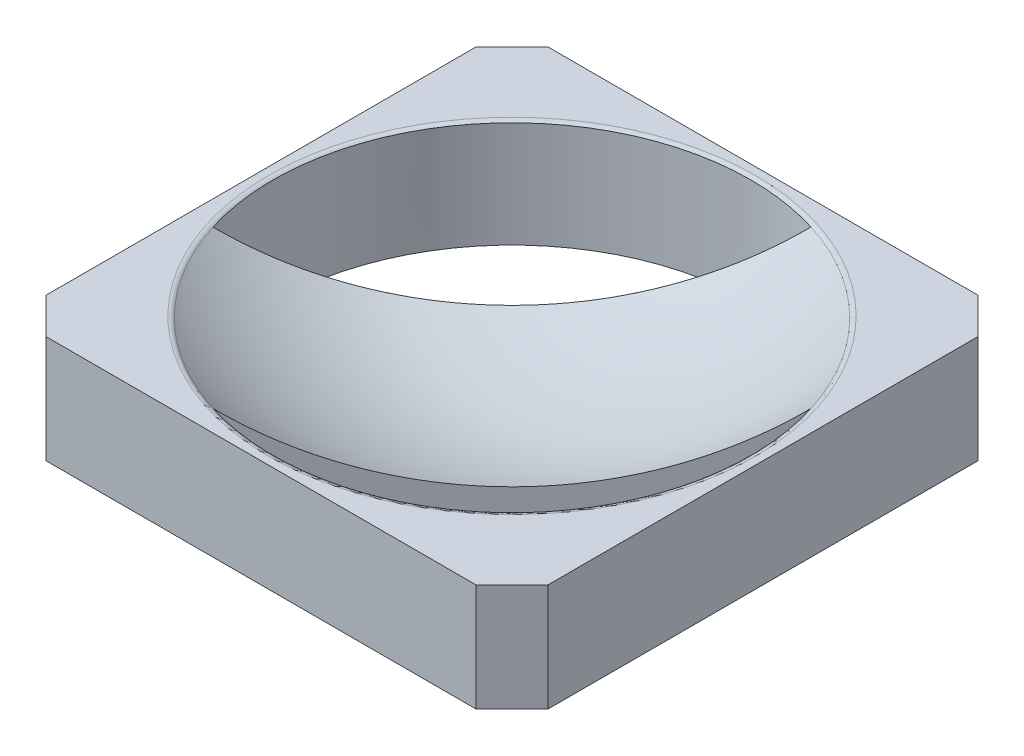
SolidWorks part; units mm, degrees
ref_plane "Front Plane" through (0, 0, 0) normal (0, 0, 1) x (1, 0, 0)
ref_plane "Top Plane" through (0, 0, 0) normal (0, 1, 0) x (1, 0, 0)
ref_plane "Right Plane" through (0, 0, 0) normal (1, 0, 0) x (0, 0, -1)
sketch "Sketch1" plane through (0, 0, 0) normal (0, 1, 0) x (1, 0, 0)
  line L1 (0, 0) -> (70, 0)
  line L2 (0, 0) -> (0, 70)
  line L3 (0, 70) -> (70, 70)
  line L4 (70, 0) -> (70, 70)
  line L5 (0, 0) -> (70, 70) construction
  line L6 (0, 70) -> (70, 0) construction
  point P4 (35, 35)
  dimension "D1" = 70
  dimension "D2" = 70
extrude "Boss-Extrude1" add sketch "Sketch1" along normal blind 15
ref_plane "Plane1" through (0, 0, -35) normal (0, 0, -1) x (-1, 0, 0)
sketch "Sketch2" plane through (0, 0, -35) normal (0, 0, -1) x (-1, 0, 0)
  line L0 (-35, 0) -> (-35, 56) construction
  line L1 (0, 0) -> (-70, 0) construction
  line L2 (-35, 109) -> (-35, 3)
  arc A0 (-35, 3) -> (-35, 109) centre (-35, 56) ccw
  dimension "D1" = 106
  dimension "D2" = 56
revolve "Cut-Revolve3" cut sketch "Sketch2" angle 360 about L0
chamfer "Chamfer1" distance 5 angle 45 4 edges at (0, 7.5, -70) (0, 7.5, 0) (70, 7.5, -70) (70, 7.5, 0)
fillet "Fillet1" radius 1 1 edges at (35, 15, -68.5857)
sketch "Sketch3" plane through (0, 15, 0) normal (0, 1, 0) x (1, 0, 0)
  line L0 (67.5, 67.5) -> (2.5, 2.5) construction
  line L1 (70, 65) -> (65, 70) construction
  line L2 (0, 5) -> (5, 0) construction
  line L3 (35, 35) -> (45.9602, 24.0398) construction
  line L4 (66.8106, 44.8902) -> (25.1098, 3.1894)
  line L8 (44.8902, 66.8106) -> (3.1894, 25.1098)
  circle A0 centre (35, 35) radius 33.3126 construction
  arc A1 (66.8106, 44.8902) -> (25.1098, 3.1894) centre (35, 35) cw
  arc A2 (44.8902, 66.8106) -> (3.1894, 25.1098) centre (35, 35) ccw
  dimension "D1" = 15.5
extrude "Cut-Extrude1" cut sketch "Sketch3" against normal blind 15
